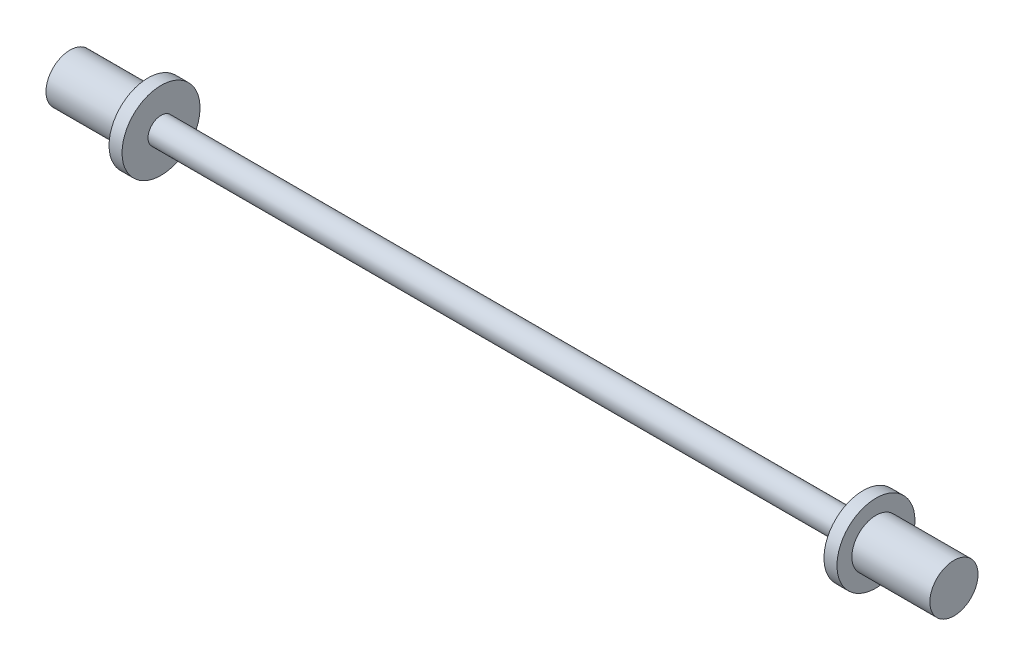
SolidWorks part; units mm, degrees
material "6061 Alloy"
ref_plane "Front Plane" through (0, 0, 0) normal (0, 0, 1) x (1, 0, 0)
ref_plane "Top Plane" through (0, 0, 0) normal (0, 1, 0) x (1, 0, 0)
ref_plane "Right Plane" through (0, 0, 0) normal (1, 0, 0) x (0, 0, -1)
sketch "Sketch2" plane through (0, 0, 0) normal (1, 0, 0) x (0, 0, -1)
  circle A0 centre (0, 0) radius 6.35
  dimension "D1" = 12.7
extrude "Boss-Extrude1" add sketch "Sketch2" along normal blind 171.45 and the other way blind 171.45
sketch "Sketch3" plane through (171.45, 0, 0) normal (1, 0, 0) x (0, 0, -1)
  circle A0 centre (0, 0) radius 19.05
  dimension "D1" = 38.1
extrude "Boss-Extrude2" add sketch "Sketch3" along normal blind 6.35
sketch "Sketch7" plane through (-171.45, 0, 0) normal (-1, 0, 0) x (0, 0, 1)
  circle A0 centre (0, 0) radius 19.05 construction
  circle A3 centre (0, 0) radius 19.05
extrude "Boss-Extrude4" add sketch "Sketch7" along normal blind 6.35
sketch "Sketch9" plane through (-177.8, 0, 0) normal (-1, 0, 0) x (0, 0, 1)
  circle A0 centre (0, 0) radius 11.77
  dimension "D1" = 23.54
extrude "Boss-Extrude6" add sketch "Sketch9" along normal blind 38.1
sketch "Sketch10" plane through (177.8, 0, 0) normal (1, 0, 0) x (0, 0, -1)
  circle A0 centre (0, 0) radius 11.77 construction
  circle A1 centre (0, 0) radius 11.77
extrude "Boss-Extrude7" add sketch "Sketch10" along normal blind 38.1
